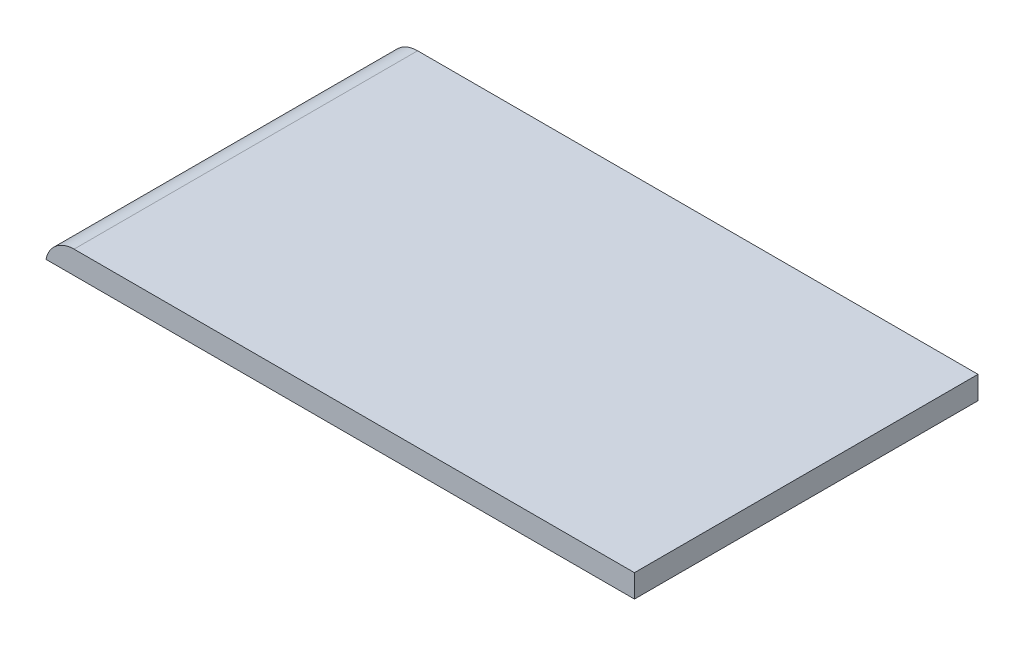
SolidWorks part; units mm, degrees
material "ABS"
ref_plane "Спереди" through (0, 0, 0) normal (0, 0, 1) x (1, 0, 0)
ref_plane "Сверху" through (0, 0, 0) normal (0, 1, 0) x (1, 0, 0)
ref_plane "Справа" through (0, 0, 0) normal (1, 0, 0) x (0, 0, -1)
sketch "Эскиз1" plane through (0, 0, 0) normal (0, 1, 0) x (1, 0, 0)
  line L1 (-61.9901, -49.4978) -> (-10.6067, -49.4978)
  line L2 (-61.9901, -49.4978) -> (-61.9901, -19.4978)
  line L3 (-61.9901, -19.4978) -> (-10.6067, -19.4978)
  line L4 (-10.6067, -49.4978) -> (-10.6067, -19.4978)
extrude "Бобышка-Вытянуть1" add sketch "Эскиз1" along normal blind 2
fillet "Скругление1" radius 2.5 1 edges at (-61.9901, 2, 34.4978)
